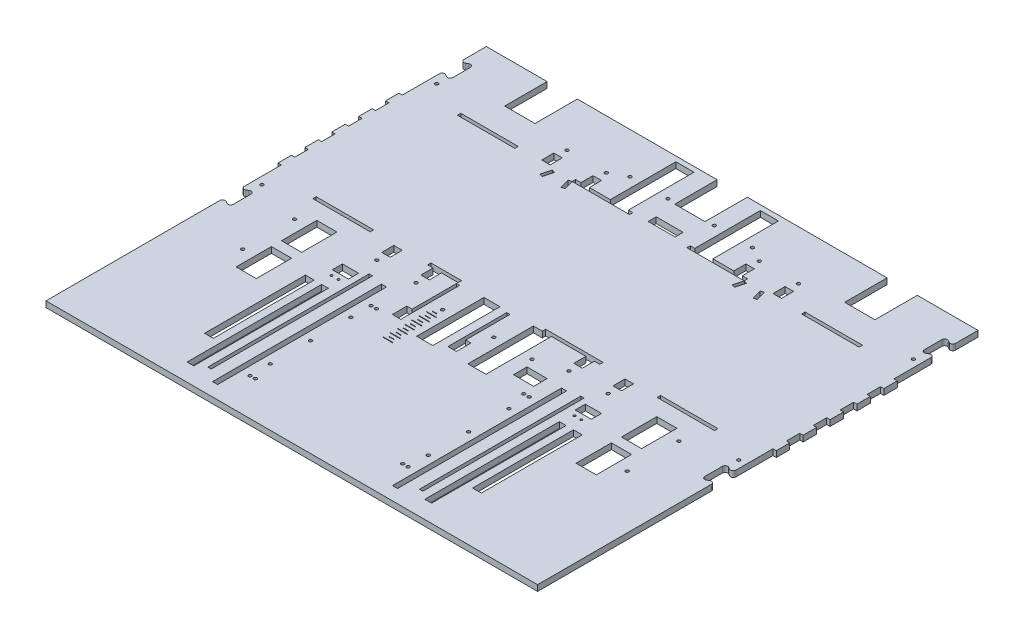
SolidWorks part; units mm, degrees
note: The reader was unsure of these and kept them because the rebuilt part matched: shared geometry of "Sketch11<3>".
material "Acrylic (Medium-high impact)"
ref_plane "Front Plane" through (0, 0, 0) normal (0, 0, 1) x (1, 0, 0)
ref_plane "Top Plane" through (0, 0, 0) normal (0, 1, 0) x (1, 0, 0)
ref_plane "Right Plane" through (0, 0, 0) normal (1, 0, 0) x (0, 0, -1)
sketch "Sketch1" plane through (0, 0, 0) normal (0, 1, 0) x (1, 0, 0)
  line L0 (0, 136.525) -> (0, -165.1) construction
  line L1 (-406.4, 136.525) -> (406.4, 136.525)
  line L2 (-406.4, 136.525) -> (-406.4, -165.1)
  line L3 (-406.4, -165.1) -> (406.4, -165.1)
  line L4 (406.4, 136.525) -> (406.4, -165.1)
  line L5 (-352.2133, 69.85) -> (-352.2133, 66.675)
  line L6 (-406.4, 69.85) -> (-352.2133, 69.85)
  line L7 (-406.4, 69.85) -> (-406.4, 66.675)
  line L8 (-406.4, 66.675) -> (-352.2133, 66.675)
  line L9 (-352.2133, 69.85) -> (-352.2133, 66.675)
  line L10 (-406.4, -66.675) -> (-352.2133, -66.675)
  line L11 (-406.4, -66.675) -> (-406.4, -69.85)
  line L12 (-406.4, -69.85) -> (-352.2133, -69.85)
  line L13 (-352.2133, -66.675) -> (-352.2133, -69.85)
  line L14 (-352.2133, 69.85) -> (-298.0267, 69.85)
  line L15 (-298.0267, 69.85) -> (-298.0267, 66.675)
  line L16 (-352.2133, 66.675) -> (-298.0267, 66.675)
  line L17 (-352.2133, -66.675) -> (-352.2133, -69.85)
  line L18 (-352.2133, -66.675) -> (-298.0267, -66.675)
  line L19 (-298.0267, -66.675) -> (-298.0267, -69.85)
  line L20 (-352.2133, -69.85) -> (-298.0267, -69.85)
  line L21 (-298.0267, 69.85) -> (-298.0267, 66.675)
  line L22 (-298.0267, 69.85) -> (-243.84, 69.85)
  line L23 (-243.84, 69.85) -> (-243.84, 66.675)
  line L24 (-298.0267, 66.675) -> (-243.84, 66.675)
  line L25 (-298.0267, -66.675) -> (-298.0267, -69.85)
  line L26 (-298.0267, -66.675) -> (-243.84, -66.675)
  line L27 (-243.84, -66.675) -> (-243.84, -69.85)
  line L28 (-298.0267, -69.85) -> (-243.84, -69.85)
  line L29 (-243.84, 69.85) -> (-243.84, 66.675)
  line L30 (-243.84, 69.85) -> (-189.6533, 69.85)
  line L31 (-189.6533, 69.85) -> (-189.6533, 66.675)
  line L32 (-243.84, 66.675) -> (-189.6533, 66.675)
  line L33 (-243.84, -66.675) -> (-243.84, -69.85)
  line L34 (-243.84, -66.675) -> (-189.6533, -66.675)
  line L35 (-189.6533, -66.675) -> (-189.6533, -69.85)
  line L36 (-243.84, -69.85) -> (-189.6533, -69.85)
  line L37 (-189.6533, 69.85) -> (-189.6533, 66.675)
  line L38 (-189.6533, 69.85) -> (-135.4667, 69.85)
  line L39 (-135.4667, 69.85) -> (-135.4667, 66.675)
  line L40 (-189.6533, 66.675) -> (-135.4667, 66.675)
  line L41 (-189.6533, -66.675) -> (-189.6533, -69.85)
  line L42 (-189.6533, -66.675) -> (-135.4667, -66.675)
  line L43 (-135.4667, -66.675) -> (-135.4667, -69.85)
  line L44 (-189.6533, -69.85) -> (-135.4667, -69.85)
  line L45 (-135.4667, 69.85) -> (-135.4667, 66.675)
  line L46 (-135.4667, 69.85) -> (-81.28, 69.85)
  line L47 (-81.28, 69.85) -> (-81.28, 66.675)
  line L48 (-135.4667, 66.675) -> (-81.28, 66.675)
  line L49 (-135.4667, -66.675) -> (-135.4667, -69.85)
  line L50 (-135.4667, -66.675) -> (-81.28, -66.675)
  line L51 (-81.28, -66.675) -> (-81.28, -69.85)
  line L52 (-135.4667, -69.85) -> (-81.28, -69.85)
  line L53 (-81.28, 69.85) -> (-81.28, 66.675)
  line L54 (-81.28, 69.85) -> (-27.0933, 69.85)
  line L55 (-27.0933, 69.85) -> (-27.0933, 66.675)
  line L56 (-81.28, 66.675) -> (-27.0933, 66.675)
  line L57 (-81.28, -66.675) -> (-81.28, -69.85)
  line L58 (-81.28, -66.675) -> (-27.0933, -66.675)
  line L59 (-27.0933, -66.675) -> (-27.0933, -69.85)
  line L60 (-81.28, -69.85) -> (-27.0933, -69.85)
  line L61 (-27.0933, 69.85) -> (-27.0933, 66.675)
  line L62 (-27.0933, 69.85) -> (27.0933, 69.85)
  line L63 (27.0933, 69.85) -> (27.0933, 66.675)
  line L64 (-27.0933, 66.675) -> (27.0933, 66.675)
  line L65 (-27.0933, -66.675) -> (-27.0933, -69.85)
  line L66 (-27.0933, -66.675) -> (27.0933, -66.675)
  line L67 (27.0933, -66.675) -> (27.0933, -69.85)
  line L68 (-27.0933, -69.85) -> (27.0933, -69.85)
  line L69 (27.0933, 69.85) -> (27.0933, 66.675)
  line L70 (27.0933, 69.85) -> (81.28, 69.85)
  line L71 (81.28, 69.85) -> (81.28, 66.675)
  line L72 (27.0933, 66.675) -> (81.28, 66.675)
  line L73 (27.0933, -66.675) -> (27.0933, -69.85)
  line L74 (27.0933, -66.675) -> (81.28, -66.675)
  line L75 (81.28, -66.675) -> (81.28, -69.85)
  line L76 (27.0933, -69.85) -> (81.28, -69.85)
  line L77 (81.28, 69.85) -> (81.28, 66.675)
  line L78 (81.28, 69.85) -> (135.4667, 69.85)
  line L79 (135.4667, 69.85) -> (135.4667, 66.675)
  line L80 (81.28, 66.675) -> (135.4667, 66.675)
  line L81 (81.28, -66.675) -> (81.28, -69.85)
  line L82 (81.28, -66.675) -> (135.4667, -66.675)
  line L83 (135.4667, -66.675) -> (135.4667, -69.85)
  line L84 (81.28, -69.85) -> (135.4667, -69.85)
  line L85 (135.4667, 69.85) -> (135.4667, 66.675)
  line L86 (135.4667, 69.85) -> (189.6533, 69.85)
  line L87 (189.6533, 69.85) -> (189.6533, 66.675)
  line L88 (135.4667, 66.675) -> (189.6533, 66.675)
  line L89 (135.4667, -66.675) -> (135.4667, -69.85)
  line L90 (135.4667, -66.675) -> (189.6533, -66.675)
  line L91 (189.6533, -66.675) -> (189.6533, -69.85)
  line L92 (135.4667, -69.85) -> (189.6533, -69.85)
  line L93 (189.6533, 69.85) -> (189.6533, 66.675)
  line L94 (189.6533, 69.85) -> (243.84, 69.85)
  line L95 (243.84, 69.85) -> (243.84, 66.675)
  line L96 (189.6533, 66.675) -> (243.84, 66.675)
  line L97 (189.6533, -66.675) -> (189.6533, -69.85)
  line L98 (189.6533, -66.675) -> (243.84, -66.675)
  line L99 (243.84, -66.675) -> (243.84, -69.85)
  line L100 (189.6533, -69.85) -> (243.84, -69.85)
  line L101 (243.84, 69.85) -> (243.84, 66.675)
  line L102 (243.84, 69.85) -> (298.0267, 69.85)
  line L103 (298.0267, 69.85) -> (298.0267, 66.675)
  line L104 (243.84, 66.675) -> (298.0267, 66.675)
  line L105 (243.84, -66.675) -> (243.84, -69.85)
  line L106 (243.84, -66.675) -> (298.0267, -66.675)
  line L107 (298.0267, -66.675) -> (298.0267, -69.85)
  line L108 (243.84, -69.85) -> (298.0267, -69.85)
  line L109 (298.0267, 69.85) -> (298.0267, 66.675)
  line L110 (298.0267, 69.85) -> (352.2133, 69.85)
  line L111 (352.2133, 69.85) -> (352.2133, 66.675)
  line L112 (298.0267, 66.675) -> (352.2133, 66.675)
  line L113 (298.0267, -66.675) -> (298.0267, -69.85)
  line L114 (298.0267, -66.675) -> (352.2133, -66.675)
  line L115 (352.2133, -66.675) -> (352.2133, -69.85)
  line L116 (298.0267, -69.85) -> (352.2133, -69.85)
  line L117 (352.2133, 69.85) -> (352.2133, 66.675)
  line L118 (352.2133, 69.85) -> (406.4, 69.85)
  line L119 (406.4, 69.85) -> (406.4, 66.675)
  line L120 (352.2133, 66.675) -> (406.4, 66.675)
  line L121 (352.2133, -66.675) -> (352.2133, -69.85)
  line L122 (352.2133, -66.675) -> (406.4, -66.675)
  line L123 (406.4, -66.675) -> (406.4, -69.85)
  line L124 (352.2133, -69.85) -> (406.4, -69.85)
  line L125 (-54.1867, 66.675) -> (-54.1867, -66.675) construction
  line L126 (-381, 57.15) -> (-381, 44.45)
  line L127 (-381, 69.85) -> (-377.825, 69.85)
  line L128 (-381, 69.85) -> (-381, 57.15)
  line L129 (-381, 57.15) -> (-377.825, 57.15)
  line L130 (-377.825, 69.85) -> (-377.825, 57.15)
  line L131 (377.825, 69.85) -> (381, 69.85)
  line L132 (377.825, 69.85) -> (377.825, 57.15)
  line L133 (377.825, 57.15) -> (381, 57.15)
  line L134 (381, 69.85) -> (381, 57.15)
  line L135 (-381, 57.15) -> (-377.825, 57.15)
  line L136 (-377.825, 57.15) -> (-377.825, 44.45)
  line L137 (-381, 44.45) -> (-377.825, 44.45)
  line L138 (377.825, 57.15) -> (377.825, 44.45)
  line L139 (377.825, 57.15) -> (381, 57.15)
  line L140 (381, 57.15) -> (381, 44.45)
  line L141 (377.825, 44.45) -> (381, 44.45)
  line L142 (-381, 44.45) -> (-381, 31.75)
  line L143 (-381, 44.45) -> (-377.825, 44.45)
  line L144 (-377.825, 44.45) -> (-377.825, 31.75)
  line L145 (-381, 31.75) -> (-377.825, 31.75)
  line L146 (377.825, 44.45) -> (377.825, 31.75)
  line L147 (377.825, 44.45) -> (381, 44.45)
  line L148 (381, 44.45) -> (381, 31.75)
  line L149 (377.825, 31.75) -> (381, 31.75)
  line L150 (-381, 31.75) -> (-381, 19.05)
  line L151 (-381, 31.75) -> (-377.825, 31.75)
  line L152 (-377.825, 31.75) -> (-377.825, 19.05)
  line L153 (-381, 19.05) -> (-377.825, 19.05)
  line L154 (377.825, 31.75) -> (377.825, 19.05)
  line L155 (377.825, 31.75) -> (381, 31.75)
  line L156 (381, 31.75) -> (381, 19.05)
  line L157 (377.825, 19.05) -> (381, 19.05)
  line L158 (-381, 19.05) -> (-381, 6.35)
  line L159 (-381, 19.05) -> (-377.825, 19.05)
  line L160 (-377.825, 19.05) -> (-377.825, 6.35)
  line L161 (-381, 6.35) -> (-377.825, 6.35)
  line L162 (377.825, 19.05) -> (377.825, 6.35)
  line L163 (377.825, 19.05) -> (381, 19.05)
  line L164 (381, 19.05) -> (381, 6.35)
  line L165 (377.825, 6.35) -> (381, 6.35)
  line L166 (-381, 6.35) -> (-381, -6.35)
  line L167 (-381, 6.35) -> (-377.825, 6.35)
  line L168 (-377.825, 6.35) -> (-377.825, -6.35)
  line L169 (-381, -6.35) -> (-377.825, -6.35)
  line L170 (377.825, 6.35) -> (377.825, -6.35)
  line L171 (377.825, 6.35) -> (381, 6.35)
  line L172 (381, 6.35) -> (381, -6.35)
  line L173 (377.825, -6.35) -> (381, -6.35)
  line L174 (-381, -6.35) -> (-381, -19.05)
  line L175 (-381, -6.35) -> (-377.825, -6.35)
  line L176 (-377.825, -6.35) -> (-377.825, -19.05)
  line L177 (-381, -19.05) -> (-377.825, -19.05)
  line L178 (377.825, -6.35) -> (377.825, -19.05)
  line L179 (377.825, -6.35) -> (381, -6.35)
  line L180 (381, -6.35) -> (381, -19.05)
  line L181 (377.825, -19.05) -> (381, -19.05)
  line L182 (-381, -19.05) -> (-381, -31.75)
  line L183 (-381, -19.05) -> (-377.825, -19.05)
  line L184 (-377.825, -19.05) -> (-377.825, -31.75)
  line L185 (-381, -31.75) -> (-377.825, -31.75)
  line L186 (377.825, -19.05) -> (377.825, -31.75)
  line L187 (377.825, -19.05) -> (381, -19.05)
  line L188 (381, -19.05) -> (381, -31.75)
  line L189 (377.825, -31.75) -> (381, -31.75)
  line L190 (-381, -31.75) -> (-381, -44.45)
  line L191 (-381, -31.75) -> (-377.825, -31.75)
  line L192 (-377.825, -31.75) -> (-377.825, -44.45)
  line L193 (-381, -44.45) -> (-377.825, -44.45)
  line L194 (377.825, -31.75) -> (377.825, -44.45)
  line L195 (377.825, -31.75) -> (381, -31.75)
  line L196 (381, -31.75) -> (381, -44.45)
  line L197 (377.825, -44.45) -> (381, -44.45)
  line L198 (-381, -44.45) -> (-381, -57.15)
  line L199 (-381, -44.45) -> (-377.825, -44.45)
  line L200 (-377.825, -44.45) -> (-377.825, -57.15)
  line L201 (-381, -57.15) -> (-377.825, -57.15)
  line L202 (377.825, -44.45) -> (377.825, -57.15)
  line L203 (377.825, -44.45) -> (381, -44.45)
  line L204 (381, -44.45) -> (381, -57.15)
  line L205 (377.825, -57.15) -> (381, -57.15)
  line L206 (-381, -57.15) -> (-381, -69.85)
  line L207 (-381, -57.15) -> (-377.825, -57.15)
  line L208 (-377.825, -57.15) -> (-377.825, -69.85)
  line L209 (-381, -69.85) -> (-377.825, -69.85)
  line L210 (377.825, -57.15) -> (377.825, -69.85)
  line L211 (377.825, -57.15) -> (381, -57.15)
  line L212 (381, -57.15) -> (381, -69.85)
  line L213 (377.825, -69.85) -> (381, -69.85)
  line L214 (-377.825, 0) -> (377.825, 0) construction
  point P23 (-54.1867, 0)
  point P133 (0, 0)
  dimension "D1" = 301.625
  dimension "D2" = 812.8
  dimension "D3" = 3.175
  dimension "D5" = 54.1867
  dimension "D6" = 66.675
  dimension "D7" = 133.35
  dimension "D9" = 12.7
  dimension "D10" = 755.65
  dimension "D4" = 15
  dimension "D8" = 11
extrude "Main Extrude" add sketch "Sketch1" along normal blind 5.588 contours L124 L116 L108 L100 L92 L84 L76 L68 L60 L52 L44 L36 L28 L20 L12 L2 L3 L4 | L210 L202 L194 L186 L178 L170 L162 L154 L146 L138 L132 L120 L112 L104 L96 L88 L80 L72 L64 L56 L48 L40 L32 L24 L16 L8 L130 L136 L144 L152 L160 L168 L176 L184 L192 L200 L208 L10 L18 L26 L34 L42 L50 L58 L66 L74 L82 L90 L98 L106 L114 | L110 L118 L4 L1 L2 L6 L14 L22 L30 L38 L46 L54 L62 L70 L78 L86 L94 L102 | L206 L198 L190 L182 L174 L166 L158 L150 L142 L126 L128 L8 L2 L10 | L204 L212 L122 L4 L120 L134 L140 L148 L156 L164 L172 L180 L188 L196 | L126 L137 L136 L129 | L150 L153 L152 L145 | L166 L169 L168 L161 | L182 L185 L184 L177 | L198 L201 L200 L193 | L13 L20 L19 L18 | L5 L16 L15 L14 | L23 L32 L31 L30 | L27 L36 L35 L34 | L43 L52 L51 L50 | L39 L48 L47 L46 | L55 L64 L63 L62 | L59 L68 L67 L66 | L71 L80 L79 L78 | L75 L84 L83 L82 | L87 L96 L95 L94 | L103 L112 L111 L110 | L91 L100 L99 L98 | L107 L116 L115 L114 | L138 L141 L140 L133 | L154 L157 L156 L149 | L170 L173 L172 L165 | L186 L189 L188 L181 | L202 L205 L204 L197
sketch "Sketch2" plane through (0, 5.588, 0) normal (0, 1, 0) x (1, 0, 0)
  line L0 (-90.678, 66.675) -> (-90.678, -110.1521) construction
  line L1 (-81.28, 66.675) -> (-27.0933, 66.675) construction
  line L3 (90.678, 66.675) -> (90.678, -110.1521) construction
  line L4 (27.0933, 66.675) -> (81.28, 66.675) construction
  line L5 (-90.678, -21.7386) -> (90.678, -21.7386) construction
  line L6 (-81.28, -66.675) -> (-27.0933, -66.675) construction
  line L7 (-52.578, -66.675) -> (-1.778, -66.675) construction
  line L8 (-52.578, -66.675) -> (-52.578, -36.2354) construction
  line L9 (-52.578, -36.2354) -> (-1.778, -36.2354) construction
  line L10 (-1.778, -66.675) -> (-1.778, -36.2354) construction
  line L11 (-26.543, 63.5) -> (26.543, 63.5) construction
  line L12 (13.843, -60.325) -> (40.513, -60.325) construction
  line L13 (13.843, -60.325) -> (13.843, -66.675) construction
  line L14 (13.843, -66.675) -> (40.513, -66.675) construction
  line L15 (40.513, -60.325) -> (40.513, -66.675) construction
  line L16 (-53.213, 66.675) -> (-26.543, 66.675) construction
  line L17 (-53.213, 66.675) -> (-53.213, 60.325) construction
  line L18 (-53.213, 60.325) -> (-26.543, 60.325) construction
  line L19 (-26.543, 66.675) -> (-26.543, 60.325) construction
  line L20 (26.543, 66.675) -> (53.213, 66.675) construction
  line L21 (26.543, 66.675) -> (26.543, 60.325) construction
  line L22 (26.543, 60.325) -> (53.213, 60.325) construction
  line L23 (53.213, 66.675) -> (53.213, 60.325) construction
  line L24 (27.0933, -66.675) -> (81.28, -66.675) construction
  point P4 (0, -21.7386)
  point P23 (-27.178, -36.2354)
  point P24 (27.178, -60.325)
  point P34 (0, 63.5)
  point P35 (-39.878, 66.675)
  dimension "D1" = 181.356
  dimension "D2" = 50.8
  dimension "D3" = 63.5
  dimension "D4" = 26.67
  dimension "D5" = 63.5
  dimension "D6" = 50.8
  dimension "D7" = 6.35
sketch "Sketch3" plane through (0, 5.588, 0) normal (0, 1, 0) x (1, 0, 0)
  line L1 (-52.578, -66.675) -> (-27.0933, -66.675)
  line L2 (-52.578, -66.675) -> (-52.578, -69.85)
  line L3 (-52.578, -69.85) -> (-27.0933, -69.85)
  line L4 (-27.0933, -66.675) -> (-27.0933, -69.85)
extrude "Under Trough Fill" add sketch "Sketch3" against normal up to surface (5.588 mm away) up to face at (0, 0, 1.5875)
sketch "Sketch4" plane through (0, 5.588, 0) normal (0, 1, 0) x (1, 0, 0)
  line L0 (-39.878, 66.675) -> (39.878, 66.675) construction
  line L2 (-406.4, 136.525) -> (406.4, 136.525) construction
  line L3 (27.0933, -69.85) -> (81.28, -69.85) construction
  line L4 (27.0933, 66.675) -> (81.28, 66.675) construction
  line L5 (27.178, -131.7625) -> (27.178, -66.675) construction
  line L6 (13.843, -66.675) -> (40.513, -66.675) construction
  line L7 (39.878, 131.7625) -> (39.878, 66.675) construction
  line L8 (-406.4, 66.675) -> (-406.4, -66.675) construction
  line L9 (-39.878, 131.7625) -> (-39.878, 66.675) construction
  line L11 (-406.4, -66.675) -> (-381, -66.675) construction
  line L12 (-400.05, -66.675) -> (-387.35, -66.675)
  line L13 (-400.05, -66.675) -> (-400.05, -63.5)
  line L14 (-400.05, -63.5) -> (-387.35, -63.5)
  line L15 (-387.35, -66.675) -> (-387.35, -63.5)
  line L16 (-406.4, 66.675) -> (-381, 66.675) construction
  line L17 (-400.05, 66.675) -> (-387.35, 66.675)
  line L18 (-400.05, 66.675) -> (-400.05, 63.5)
  line L19 (-400.05, 63.5) -> (-387.35, 63.5)
  line L20 (-387.35, 66.675) -> (-387.35, 63.5)
  line L21 (381, 66.675) -> (406.4, 66.675) construction
  line L22 (387.35, 66.675) -> (400.05, 66.675)
  line L23 (387.35, 66.675) -> (387.35, 63.5)
  line L24 (387.35, 63.5) -> (400.05, 63.5)
  line L25 (400.05, 66.675) -> (400.05, 63.5)
  line L26 (381, -66.675) -> (406.4, -66.675) construction
  line L27 (387.35, -66.675) -> (400.05, -66.675)
  line L28 (387.35, -66.675) -> (387.35, -63.5)
  line L29 (387.35, -63.5) -> (400.05, -63.5)
  line L30 (400.05, -66.675) -> (400.05, -63.5)
  line L35 (406.4, 66.675) -> (406.4, -66.675) construction
  line L36 (-81.28, 69.85) -> (-27.0933, 69.85) construction
  line L39 (27.0933, 69.85) -> (81.28, 69.85) construction
  line L40 (18.628, -69.85) -> (35.728, -69.85)
  line L41 (18.628, -69.85) -> (18.628, -131.7625)
  line L42 (18.628, -131.7625) -> (35.728, -131.7625)
  line L43 (35.728, -69.85) -> (35.728, -131.7625)
  line L44 (31.328, 131.7625) -> (48.428, 131.7625)
  line L45 (31.328, 131.7625) -> (31.328, 69.85)
  line L46 (31.328, 69.85) -> (48.428, 69.85)
  line L47 (48.428, 131.7625) -> (48.428, 69.85)
  line L48 (9.178, -97.7625) -> (45.178, -97.7625) construction
  line L49 (-48.428, 131.7625) -> (-31.328, 131.7625)
  line L50 (-48.428, 131.7625) -> (-48.428, 69.85)
  line L51 (-48.428, 69.85) -> (-31.328, 69.85)
  line L52 (-31.328, 131.7625) -> (-31.328, 69.85)
  line L53 (-57.878, 97.7625) -> (-21.878, 97.7625) construction
  line L54 (21.878, 97.7625) -> (57.878, 97.7625) construction
  circle A12 centre (9.178, -97.7625) radius 1.5
  circle A13 centre (45.178, -97.7625) radius 1.5
  circle A14 centre (21.878, 97.7625) radius 1.5
  circle A15 centre (57.878, 97.7625) radius 1.5
  circle A16 centre (-21.878, 97.7625) radius 1.5
  circle A17 centre (-57.878, 97.7625) radius 1.5
  point P2 (0, 136.525)
  point P3 (0, 66.675)
  point P59 (-393.7, -63.5)
  point P62 (393.7, -66.675)
  point P73 (27.178, -69.85)
  point P87 (39.878, 131.7625)
  point P92 (-39.878, 131.7625)
  point P100 (27.178, -97.7625)
  point P106 (-39.878, 97.7625)
  point P107 (39.878, 97.7625)
  dimension "D2" = 62.656
  dimension "D15" = 3
  dimension "D4" = 12.7
  dimension "D5" = 3.175
  dimension "D6" = 12.7
  dimension "D7" = 12.7
  dimension "D12" = 17.1
  dimension "D13" = 61.9125
  dimension "D14" = 36
  dimension "D16" = 27.9125
  dimension "D17" = 27.9125
extrude "Lever Holes" cut sketch "Sketch4" against normal through all
sketch "Sketch5" plane through (0, 5.588, 0) normal (0, 1, 0) x (1, 0, 0)
  line L0 (-20.498, -133.35) -> (-20.498, -69.85) construction
  line L1 (-49.428, -99.2124) -> (-4.928, -99.2124) construction
  line L2 (-52.428, -127) -> (-49.428, -127)
  line L3 (-52.428, -127) -> (-52.428, -71.4248)
  line L4 (-52.428, -71.4248) -> (-49.428, -71.4248)
  line L5 (-49.428, -127) -> (-49.428, -71.4248)
  line L6 (-4.928, -127) -> (-1.928, -127)
  line L7 (-4.928, -127) -> (-4.928, -71.4248)
  line L8 (-4.928, -71.4248) -> (-1.928, -71.4248)
  line L9 (-1.928, -127) -> (-1.928, -71.4248)
  line L10 (-27.178, -66.675) -> (-27.178, -99.2124) construction
  line L11 (-52.578, -66.675) -> (-1.778, -66.675) construction
  line L12 (-28.118, -69.85) -> (-12.878, -69.85)
  line L13 (-81.28, -69.85) -> (-52.578, -69.85) construction
  line L14 (-55.778, -71.9185) -> (-4.928, -71.9185) construction
  line L15 (-28.118, -69.85) -> (-28.118, -133.35)
  line L16 (-52.578, -66.675) -> (-52.578, -69.85) construction
  line L17 (-52.428, -127) -> (-57.428, -127)
  line L18 (-52.428, -127) -> (-52.428, -113.3)
  line L19 (-52.428, -113.3) -> (-57.428, -113.3)
  line L20 (-57.428, -127) -> (-57.428, -113.3)
  line L21 (-1.928, -127) -> (3.072, -127)
  line L22 (-1.928, -127) -> (-1.928, -113.3)
  line L23 (-1.928, -113.3) -> (3.072, -113.3)
  line L24 (3.072, -127) -> (3.072, -113.3)
  line L25 (-52.578, -66.675) -> (-52.428, -66.675)
  line L26 (-52.578, -66.675) -> (-52.578, -69.85)
  line L27 (-52.578, -69.85) -> (-52.428, -69.85)
  line L28 (-52.428, -66.675) -> (-52.428, -69.85)
  line L29 (-28.118, -133.35) -> (-12.878, -133.35)
  line L30 (-12.878, -69.85) -> (-12.878, -133.35)
  line L31 (-81.28, -69.85) -> (-52.578, -69.85) construction
  circle A0 centre (-3.428, -99.35) radius 1.5
  circle A2 centre (-37.568, -99.35) radius 1.5
  point P19 (-50.928, -127)
  point P20 (-3.428, -127)
  dimension "D6" = 3
  dimension "D1" = 3
  dimension "D3" = 47.5
  dimension "D4" = 57.15
  dimension "D7" = 5
  dimension "D8" = 13.7
  dimension "D2" = 1.5748
  dimension "D5" = 15.24
  dimension "D9" = 63.5
  dimension "D10" = 7.95
  dimension "D11" = 9.45
  dimension "D12" = 34
extrude "Trough Slot" cut sketch "Sketch5" against normal through all
sketch "Sketch6" plane through (0, 5.588, 0) normal (0, 1, 0) x (1, 0, 0)
  line L0 (90.678, -130.35) -> (103.378, -130.35) construction
  line L1 (-114.6905, -123.85) -> (114.6905, -123.85) construction
  line L3 (-81.28, -69.85) -> (-52.428, -69.85) construction
  line L4 (111.4405, -123.85) -> (117.9405, -123.85) construction
  line L5 (95.4405, -130.35) -> (95.4405, -83.0238) construction
  line L6 (90.678, 66.675) -> (90.678, -110.1521) construction
  line L7 (0, -21.7386) -> (0, -165.1) construction
  line L8 (-90.678, -21.7386) -> (90.678, -21.7386) construction
  line L9 (-406.4, -165.1) -> (406.4, -165.1) construction
  line L20 (-117.9405, -123.85) -> (-111.4405, -123.85) construction
  line L21 (-122.3105, -109.245) -> (-107.0705, -109.245)
  line L22 (-122.3105, -109.245) -> (-122.3105, -118.77)
  line L23 (-122.3105, -118.77) -> (-107.0705, -118.77)
  line L24 (-107.0705, -109.245) -> (-107.0705, -118.77)
  line L25 (107.0705, -109.245) -> (122.3105, -109.245)
  line L26 (107.0705, -109.245) -> (107.0705, -118.77)
  line L27 (107.0705, -118.77) -> (122.3105, -118.77)
  line L28 (122.3105, -109.245) -> (122.3105, -118.77)
  line L29 (-114.6905, -118.77) -> (-114.6905, -123.85) construction
  line L30 (114.6905, -118.77) -> (114.6905, -123.85) construction
  circle A0 centre (117.9405, -123.85) radius 1.05
  circle A1 centre (111.4405, -123.85) radius 1.05
  circle A10 centre (-117.9405, -123.85) radius 1.05
  circle A11 centre (-111.4405, -123.85) radius 1.05
  point P0 (108.1405, -130.35)
  point P11 (0, -123.85)
  dimension "D5" = 2.1
  dimension "D2" = 60.5
  dimension "D3" = 6.5
  dimension "D4" = 12.7
  dimension "D6" = 6.5
  dimension "D7" = 4.7625
  dimension "D8" = 3.3
  dimension "D9" = 5.08
  dimension "D10" = 9.525
  dimension "D11" = 15.24
extrude "Close Switch Holes" cut sketch "Sketch6" against normal through all
sketch "Sketch7" plane through (0, 5.588, 0) normal (0, 1, 0) x (1, 0, 0)
  line L0 (-38.773, -149.85) -> (-38.773, -105.4) construction
  line L1 (-49.428, -127) -> (-28.118, -127) construction
  line L2 (-49.428, -127) -> (-49.428, -71.4248) construction
  line L4 (-28.118, -69.85) -> (-28.118, -133.35) construction
  line L9 (-81.28, -69.85) -> (-52.428, -69.85) construction
  line L10 (-43.5355, -142.738) -> (-43.5355, -143.246)
  line L15 (-43.5355, -149.596) -> (-34.0105, -149.596)
  line L16 (-43.5355, -149.596) -> (-43.5355, -150.104)
  line L21 (-43.5355, -150.104) -> (-34.0105, -150.104)
  line L22 (-34.0105, -149.596) -> (-34.0105, -150.104)
  line L27 (-43.5355, -149.596) -> (-34.0105, -150.104) construction
  line L28 (-43.5355, -150.104) -> (-34.0105, -149.596) construction
  line L33 (-41.1542, -146.421) -> (-36.3917, -146.421)
  line L34 (-41.1542, -146.421) -> (-41.1542, -146.929)
  line L39 (-41.1542, -146.929) -> (-36.3917, -146.929)
  line L40 (-36.3917, -146.421) -> (-36.3917, -146.929)
  line L45 (-41.1542, -146.421) -> (-36.3917, -146.929) construction
  line L46 (-41.1542, -146.929) -> (-36.3917, -146.421) construction
  line L51 (-43.5355, -142.738) -> (-34.0105, -142.738)
  line L52 (-34.0105, -142.738) -> (-34.0105, -143.246)
  line L57 (-43.5355, -143.246) -> (-34.0105, -143.246)
  line L58 (-41.1542, -139.563) -> (-41.1542, -140.071)
  line L63 (-41.1542, -139.563) -> (-36.3917, -139.563)
  line L64 (-36.3917, -139.563) -> (-36.3917, -140.071)
  line L69 (-41.1542, -140.071) -> (-36.3917, -140.071)
  line L70 (-43.5355, -135.88) -> (-43.5355, -136.388)
  line L75 (-43.5355, -135.88) -> (-34.0105, -135.88)
  line L76 (-34.0105, -135.88) -> (-34.0105, -136.388)
  line L81 (-43.5355, -136.388) -> (-34.0105, -136.388)
  line L82 (-41.1543, -132.705) -> (-41.1543, -133.213)
  line L83 (-41.1543, -132.705) -> (-36.3918, -132.705)
  line L84 (-36.3918, -132.705) -> (-36.3918, -133.213)
  line L85 (-41.1543, -133.213) -> (-36.3918, -133.213)
  line L86 (-43.5355, -129.022) -> (-43.5355, -129.53)
  line L87 (-43.5355, -129.022) -> (-34.0105, -129.022)
  line L88 (-34.0105, -129.022) -> (-34.0105, -129.53)
  line L89 (-43.5355, -129.53) -> (-34.0105, -129.53)
  line L90 (-41.1543, -125.847) -> (-41.1543, -126.355)
  line L91 (-41.1543, -125.847) -> (-36.3918, -125.847)
  line L92 (-36.3918, -125.847) -> (-36.3918, -126.355)
  line L93 (-41.1543, -126.355) -> (-36.3918, -126.355)
  line L94 (-43.5355, -122.164) -> (-43.5355, -122.672)
  line L95 (-43.5355, -122.164) -> (-34.0105, -122.164)
  line L96 (-34.0105, -122.164) -> (-34.0105, -122.672)
  line L97 (-43.5355, -122.672) -> (-34.0105, -122.672)
  line L98 (-41.1543, -118.989) -> (-41.1543, -119.497)
  line L99 (-41.1543, -118.989) -> (-36.3918, -118.989)
  line L100 (-36.3918, -118.989) -> (-36.3918, -119.497)
  line L101 (-41.1543, -119.497) -> (-36.3918, -119.497)
  line L102 (-43.5355, -115.306) -> (-43.5355, -115.814)
  line L103 (-43.5355, -115.306) -> (-34.0105, -115.306)
  line L104 (-34.0105, -115.306) -> (-34.0105, -115.814)
  line L105 (-43.5355, -115.814) -> (-34.0105, -115.814)
  line L106 (-41.1543, -112.131) -> (-41.1543, -112.639)
  line L107 (-41.1543, -112.131) -> (-36.3918, -112.131)
  line L108 (-36.3918, -112.131) -> (-36.3918, -112.639)
  line L109 (-41.1543, -112.639) -> (-36.3918, -112.639)
  line L130 (-28.5048, -105.4) -> (-38.773, -105.4) construction
  line L136 (-43.5355, -108.448) -> (-43.5355, -108.956)
  line L137 (-43.5355, -108.448) -> (-34.0105, -108.448)
  line L138 (-34.0105, -108.448) -> (-34.0105, -108.956)
  line L139 (-43.5355, -108.956) -> (-34.0105, -108.956)
  line L140 (-41.1543, -105.273) -> (-41.1543, -105.781)
  line L141 (-41.1543, -105.273) -> (-36.3918, -105.273)
  line L142 (-36.3918, -105.273) -> (-36.3918, -105.781)
  line L143 (-41.1543, -105.781) -> (-36.3918, -105.781)
  point P2 (-38.773, -146.675)
  point P16 (-41.1542, -146.675)
  point P17 (-43.5355, -149.85)
  point P65 (-38.773, -127)
  dimension "D1" = 80
  dimension "D2" = 44.45
  dimension "D3" = 0.508
  dimension "D4" = 9.525
  dimension "D5" = 3.175
  dimension "D6" = 4.7625
  dimension "D8" = 3.175
  dimension "D7" = 7
extrude "Trough Measurement" cut sketch "Sketch7" against normal through all
sketch "Sketch8" plane through (0, 5.588, 0) normal (0, 1, 0) x (1, 0, 0)
  line L0 (160.528, 96.525) -> (160.528, -85.725) construction
  line L1 (49.063, -106.3625) -> (68.113, -106.3625)
  line L2 (49.063, -106.3625) -> (49.063, -119.0625)
  line L3 (49.063, -119.0625) -> (68.113, -119.0625)
  line L4 (68.113, -106.3625) -> (68.113, -119.0625)
  line L5 (35.728, -131.7625) -> (35.728, -69.85) construction
  line L6 (135.4667, -69.85) -> (189.6533, -69.85) construction
  line L15 (-406.4, 136.525) -> (406.4, 136.525) construction
  line L16 (-31.328, 123) -> (31.328, 123) construction
  line L17 (-31.328, 69.85) -> (-31.328, 131.7625) construction
  line L18 (31.328, 131.7625) -> (31.328, 69.85) construction
  line L19 (0, 77.47) -> (0, 96.525) construction
  line L20 (18.628, -131.7625) -> (35.728, -131.7625) construction
  line L29 (151.003, -119.0625) -> (170.053, -119.0625)
  line L30 (-174.8155, 136.525) -> (-146.2405, 136.525)
  line L31 (-14.2875, 136.525) -> (14.2875, 136.525)
  line L32 (-14.2875, 136.525) -> (-14.2875, 96.525)
  line L33 (-14.2875, 96.525) -> (14.2875, 96.525)
  line L34 (14.2875, 136.525) -> (14.2875, 96.525)
  line L35 (-12.7, 69.85) -> (12.7, 69.85)
  line L36 (-12.7, 69.85) -> (-12.7, 77.47)
  line L37 (-12.7, 77.47) -> (12.7, 77.47)
  line L38 (12.7, 69.85) -> (12.7, 77.47)
  line L39 (-31.328, 69.85) -> (-27.0933, 69.85) construction
  line L40 (151.003, -85.725) -> (170.053, -85.725)
  line L41 (151.003, -85.725) -> (151.003, -161.925)
  line L42 (151.003, -161.925) -> (170.053, -161.925)
  line L43 (170.053, -85.725) -> (170.053, -161.925)
  line L44 (-170.053, -85.725) -> (-151.003, -85.725)
  line L45 (-170.053, -85.725) -> (-170.053, -161.925)
  line L46 (-170.053, -161.925) -> (-151.003, -161.925)
  line L47 (-151.003, -85.725) -> (-151.003, -161.925)
  line L48 (90.678, 66.675) -> (90.678, -110.1521) construction
  line L49 (-151.003, -123.825) -> (151.003, -123.825) construction
  line L50 (151.003, -119.0625) -> (151.003, -128.5875)
  line L51 (151.003, -128.5875) -> (170.053, -128.5875)
  line L52 (170.053, -119.0625) -> (170.053, -128.5875)
  line L53 (-170.053, -119.0625) -> (-151.003, -119.0625)
  line L54 (-170.053, -119.0625) -> (-170.053, -128.5875)
  line L55 (-170.053, -128.5875) -> (-151.003, -128.5875)
  line L56 (-151.003, -119.0625) -> (-151.003, -128.5875)
  line L57 (-174.8155, 136.525) -> (-174.8155, 96.525)
  line L58 (-174.8155, 96.525) -> (-146.2405, 96.525)
  line L59 (-146.2405, 136.525) -> (-146.2405, 96.525)
  line L60 (146.2405, 136.525) -> (174.8155, 136.525)
  line L61 (146.2405, 136.525) -> (146.2405, 96.525)
  line L62 (146.2405, 96.525) -> (174.8155, 96.525)
  line L63 (174.8155, 136.525) -> (174.8155, 96.525)
  line L64 (-160.528, 96.525) -> (-160.528, -85.725) construction
  point P6 (58.588, -106.3625)
  point P23 (0, 123)
  point P30 (170.053, -123.825)
  point P31 (170.053, -123.825)
  point P38 (0, 96.525)
  point P61 (0, -123.825)
  dimension "D1" = 19.05
  dimension "D2" = 12.7
  dimension "D3" = 22.86
  dimension "D4" = 12.7
  dimension "D5" = 9.525
  dimension "D6" = 76.2
  dimension "D8" = 40
  dimension "D9" = 28.575
  dimension "D10" = 7.62
  dimension "D11" = 25.4
  dimension "D12" = 15.875
  dimension "D13" = 60.325
  dimension "D15" = 19.05
extrude "Wire Holes" cut sketch "Sketch8" against normal through all contours L55 L45 L46 L47 | L45 L53 L47 L44 | L51 L41 L42 L43 | L43 L40 L41 L29 | L4 L1 L2 L3 | L34 L31 L32 L33 | L35 L38 L37 L36 | L59 L30 L57 L58 | L63 L60 L61 L62
sketch "Sketch9" plane through (0, 5.588, 0) normal (0, 1, 0) x (1, 0, 0)
  line L0 (-109.2096, 89.85) -> (109.2096, 89.85) construction
  line L1 (109.2096, 89.85) -> (109.2096, -89.85) construction
  line L2 (109.2096, -89.85) -> (-109.2096, -89.85) construction
  line L3 (-109.2096, -89.85) -> (-109.2096, 89.85) construction
  line L4 (-162.56, 66.675) -> (-162.56, -66.675) construction
  line L5 (-189.6533, 66.675) -> (-135.4667, 66.675) construction
  line L6 (-189.6533, -66.675) -> (-135.4667, -66.675) construction
  line L7 (-109.2096, 0) -> (-162.56, 0) construction
  line L8 (-90.678, 66.675) -> (-90.678, -110.1521) construction
  line L9 (-189.6533, -69.85) -> (-135.4667, -69.85) construction
  line L10 (-189.6533, 69.85) -> (-135.4667, 69.85) construction
  line L11 (-113.2096, 69.85) -> (-105.2096, 69.85)
  line L12 (-113.2096, 69.85) -> (-113.2096, 81.28)
  line L13 (-113.2096, 81.28) -> (-105.2096, 81.28)
  line L14 (-105.2096, 69.85) -> (-105.2096, 81.28)
  line L16 (105.2096, 81.28) -> (113.2096, 81.28)
  line L17 (105.2096, 81.28) -> (105.2096, 69.85)
  line L18 (105.2096, 69.85) -> (113.2096, 69.85)
  line L19 (113.2096, 81.28) -> (113.2096, 69.85)
  line L20 (105.2096, -69.85) -> (113.2096, -69.85)
  line L21 (105.2096, -69.85) -> (105.2096, -81.28)
  line L22 (105.2096, -81.28) -> (113.2096, -81.28)
  line L23 (113.2096, -69.85) -> (113.2096, -81.28)
  line L24 (-113.2096, -81.28) -> (-105.2096, -81.28)
  line L25 (-113.2096, -81.28) -> (-113.2096, -69.85)
  line L26 (-113.2096, -69.85) -> (-105.2096, -69.85)
  line L27 (-105.2096, -81.28) -> (-105.2096, -69.85)
  circle A0 centre (109.2096, -89.85) radius 1.5
  circle A1 centre (-109.2096, -89.85) radius 1.5
  circle A2 centre (109.2096, 89.85) radius 1.5
  circle A3 centre (-109.2096, 89.85) radius 1.5
  point P8 (0, -89.85)
  point P29 (-109.2096, 81.28)
  point P43 (109.2096, 81.28)
  point P47 (109.2096, -69.85)
  dimension "D1" = 3
  dimension "D2" = 18.5316
  dimension "D3" = 20
  dimension "D4" = 11.43
  dimension "D5" = 8
extrude "IR Slots" cut sketch "Sketch9" against normal through all
sketch "Sketch10" plane through (0, 5.588, 0) normal (0, 1, 0) x (1, 0, 0)
  line L0 (0, 0) -> (0, 69.85) construction
  line L1 (-100.061, 66.675) -> (-96.9942, 65.8532)
  line L2 (-100.061, 66.675) -> (-102.5263, 57.4746)
  line L3 (-102.5263, 57.4746) -> (-99.4594, 56.6528)
  line L4 (-96.9942, 65.8532) -> (-99.4594, 56.6528)
  line L5 (-84.3618, 65.8532) -> (-81.295, 66.675)
  line L6 (-84.3618, 65.8532) -> (-81.8966, 56.6528)
  line L7 (-81.8966, 56.6528) -> (-78.8297, 57.4746)
  line L8 (-81.295, 66.675) -> (-78.8297, 57.4746)
  line L9 (-12.7, 69.85) -> (12.7, 69.85) construction
  line L14 (81.28, 66.675) -> (100.061, 66.675) construction
  line L19 (-90.678, 66.675) -> (-90.678, -110.1521) construction
  line L20 (-98.2268, 61.253) -> (-83.1292, 61.253) construction
  line L21 (-81.28, 66.675) -> (-100.061, 66.675) construction
  line L22 (98.2268, 61.253) -> (83.1292, 61.253) construction
  line L23 (81.295, 66.675) -> (78.8297, 57.4746)
  line L24 (81.8966, 56.6528) -> (78.8297, 57.4746)
  line L25 (84.3618, 65.8532) -> (81.8966, 56.6528)
  line L26 (84.3618, 65.8532) -> (81.295, 66.675)
  line L27 (96.9942, 65.8532) -> (99.4594, 56.6528)
  line L28 (102.5263, 57.4746) -> (99.4594, 56.6528)
  line L29 (100.061, 66.675) -> (102.5263, 57.4746)
  line L30 (100.061, 66.675) -> (96.9942, 65.8532)
  line L31 (-96.9942, 65.8532) -> (-96.774, 66.675) construction
  line L32 (-84.3618, 65.8532) -> (-84.582, 66.675) construction
  line L33 (-90.678, 66.675) -> (-90.678, 61.253) construction
  line L34 (-96.774, 66.675) -> (-95.9233, 69.85) construction
  line L35 (-84.582, 66.675) -> (-85.4327, 69.85) construction
  line L36 (-81.28, 69.85) -> (-95.9233, 69.85) construction
  point P27 (-90.678, 61.253)
  dimension "D1" = 3.175
  dimension "D3" = 9.525
  dimension "D4" = 105
  dimension "D2" = 6.096
extrude "Door Flange Slots" cut sketch "Sketch10" against normal through all
sketch "Sketch12" plane through (0, 5.588, 0) normal (0, 1, 0) x (1, 0, 0)
  line L0 (-253.5873, 82.55) -> (-225.1393, 82.55) construction
  line L1 (-253.5873, -82.55) -> (-225.1393, -82.55) construction
  line L2 (-233.807, 82.55) -> (-233.807, -82.55) construction
  line L3 (-233.807, 0) -> (0, 0) construction
  line L4 (-298.0267, -69.85) -> (-243.84, -69.85) construction
  line L5 (-240.9508, -76.2) -> (-237.7758, -76.2)
  line L6 (-240.9508, -76.2) -> (-240.9507, -88.9)
  line L7 (-240.9507, -88.9) -> (-237.7758, -88.9)
  line L8 (-237.7758, -76.2) -> (-237.7758, -88.9)
  line L9 (-240.9508, 88.9) -> (-237.7758, 88.9)
  line L10 (-240.9508, 88.9) -> (-240.9508, 76.2)
  line L11 (-240.9508, 76.2) -> (-237.7758, 76.2)
  line L12 (-237.7758, 88.9) -> (-237.7758, 76.2)
  line L13 (0, -3.0734) -> (0, 3.0734) construction
  line L14 (233.807, 82.55) -> (233.807, -82.55) construction
  line L15 (253.5873, -82.55) -> (225.1393, -82.55) construction
  line L16 (253.5873, 82.55) -> (225.1393, 82.55) construction
  line L17 (237.7758, 88.9) -> (237.7758, 76.2)
  line L18 (240.9508, 76.2) -> (237.7758, 76.2)
  line L19 (240.9508, 88.9) -> (240.9508, 76.2)
  line L20 (240.9508, 88.9) -> (237.7758, 88.9)
  line L21 (237.7757, -76.2) -> (237.7757, -88.9)
  line L22 (240.9507, -88.9) -> (237.7757, -88.9)
  line L23 (240.9507, -76.2) -> (240.9507, -88.9)
  line L24 (240.9507, -76.2) -> (237.7757, -76.2)
  circle A0 centre (-253.5873, -82.55) radius 1.5
  circle A1 centre (-225.1393, -82.55) radius 1.5
  circle A2 centre (-253.5873, 82.55) radius 1.5
  circle A3 centre (-225.1393, 82.55) radius 1.5
  circle A4 centre (225.1393, 82.55) radius 1.5
  circle A5 centre (253.5873, 82.55) radius 1.5
  circle A6 centre (225.1393, -82.55) radius 1.5
  circle A7 centre (253.5873, -82.55) radius 1.5
  point P8 (-239.3633, -76.2)
  point P9 (-239.3633, -82.55)
  point P13 (-237.7758, -82.55)
  point P14 (-239.3633, 88.9)
  point P19 (-239.3633, 82.55)
  point P22 (-240.9508, 82.55)
  dimension "D1" = 3
  dimension "D2" = 233.807
  dimension "D3" = 28.448
  dimension "D4" = 3.175
  dimension "D5" = 12.7
  dimension "D6" = 7.9375
  dimension "D7" = 12.7
extrude "Floor Mount Holes" cut sketch "Sketch12" against normal through all
sketch "Sketch11" plane through (0, 5.588, 0) normal (0, 1, 0) x (1, 0, 0)
  line L0 (-232.1306, 69.85) -> (-232.1306, 57.15)
  line L1 (-228.3206, 94.2747) -> (-226.4156, 93.1749)
  line L2 (-232.1306, 57.15) -> (-235.3056, 57.15)
  line L3 (-235.3056, 57.15) -> (-235.3056, 44.45)
  line L4 (-235.3056, 44.45) -> (-232.1306, 44.45)
  line L5 (-381, 57.15) -> (-377.825, 57.15) construction
  line L6 (-377.825, 44.45) -> (-377.825, 31.75) construction
  line L7 (-298.0267, 69.85) -> (-243.84, 69.85) construction
  line L8 (-232.1306, 44.45) -> (-232.1306, 31.75)
  line L9 (-232.1306, 31.75) -> (-235.3056, 31.75)
  line L10 (-235.3056, 31.75) -> (-235.3056, 19.05)
  line L11 (-235.3056, 19.05) -> (-232.1306, 19.05)
  line L12 (-232.1306, 19.05) -> (-232.1306, 6.35)
  line L13 (-232.1306, 6.35) -> (-235.3056, 6.35)
  line L14 (-235.3056, 6.35) -> (-235.3056, -6.35)
  line L15 (-235.3056, -6.35) -> (-232.1306, -6.35)
  line L16 (-232.1306, -6.35) -> (-232.1306, -19.05)
  line L17 (-232.1306, -19.05) -> (-235.3056, -19.05)
  line L18 (-235.3056, -19.05) -> (-235.3056, -31.75)
  line L19 (-235.3056, -31.75) -> (-232.1306, -31.75)
  line L20 (-232.1306, -31.75) -> (-232.1306, -44.45)
  line L21 (-232.1306, -44.45) -> (-235.3056, -44.45)
  line L22 (-235.3056, -44.45) -> (-235.3056, -57.15)
  line L23 (-235.3056, -57.15) -> (-232.1306, -57.15)
  line L24 (-232.1306, -57.15) -> (-232.1306, -69.85)
  line L25 (-232.1306, 69.85) -> (-232.1306, 92.075)
  line L26 (-222.6056, 95.3746) -> (-222.6056, 111.9757)
  line L27 (-226.4156, 114.1754) -> (-228.3206, 113.0756)
  line L28 (-232.1306, -118.4503) -> (-406.4, -118.4503)
  line L29 (-235.3056, -69.85) -> (-235.3056, -82.55)
  line L30 (-235.3056, -82.55) -> (-232.1306, -82.55)
  line L31 (-232.1306, -69.85) -> (-235.3056, -69.85)
  line L32 (-232.1306, -69.85) -> (-232.1306, -92.075)
  line L33 (-232.1306, 115.2753) -> (-232.1306, 136.525)
  line L34 (-406.4, 136.525) -> (-174.8155, 136.525) construction
  line L35 (-228.3206, -94.2747) -> (-226.4156, -93.1749)
  line L36 (-222.6056, -95.3746) -> (-222.6056, -111.9757)
  line L37 (-226.4156, -114.1754) -> (-228.3206, -113.0756)
  line L38 (-232.1306, -115.2753) -> (-232.1306, -165.1)
  line L39 (-406.4, -165.1) -> (406.4, -165.1) construction
  line L40 (0, -3.0734) -> (0, 3.0734) construction
  line L41 (-232.1306, 110.8759) -> (-232.1306, 96.4744) construction
  line L42 (-232.1306, -96.4744) -> (-232.1306, -110.8759) construction
  line L43 (232.1306, -96.4744) -> (232.1306, -110.8759) construction
  line L44 (232.1306, 110.8759) -> (232.1306, 96.4744) construction
  line L45 (232.1306, -115.2753) -> (232.1306, -165.1)
  line L46 (226.4156, -114.1754) -> (228.3206, -113.0756)
  line L47 (222.6056, -95.3746) -> (222.6056, -111.9757)
  line L48 (228.3206, -94.2747) -> (226.4156, -93.1749)
  line L49 (232.1306, 115.2753) -> (232.1306, 136.525)
  line L50 (232.1306, -69.85) -> (232.1306, -92.075)
  line L51 (226.4156, 114.1754) -> (228.3206, 113.0756)
  line L52 (222.6056, 95.3746) -> (222.6056, 111.9757)
  line L53 (232.1306, 69.85) -> (232.1306, 92.075)
  line L54 (232.1306, -57.15) -> (232.1306, -69.85)
  line L55 (235.3056, -57.15) -> (232.1306, -57.15)
  line L56 (235.3056, -44.45) -> (235.3056, -57.15)
  line L57 (232.1306, -44.45) -> (235.3056, -44.45)
  line L58 (232.1306, -31.75) -> (232.1306, -44.45)
  line L59 (235.3056, -31.75) -> (232.1306, -31.75)
  line L60 (235.3056, -19.05) -> (235.3056, -31.75)
  line L61 (232.1306, -19.05) -> (235.3056, -19.05)
  line L62 (232.1306, -6.35) -> (232.1306, -19.05)
  line L63 (235.3056, -6.35) -> (232.1306, -6.35)
  line L64 (235.3056, 6.35) -> (235.3056, -6.35)
  line L65 (232.1306, 6.35) -> (235.3056, 6.35)
  line L66 (232.1306, 19.05) -> (232.1306, 6.35)
  line L67 (235.3056, 19.05) -> (232.1306, 19.05)
  line L68 (235.3056, 31.75) -> (235.3056, 19.05)
  line L69 (232.1306, 31.75) -> (235.3056, 31.75)
  line L70 (232.1306, 44.45) -> (232.1306, 31.75)
  line L71 (235.3056, 44.45) -> (232.1306, 44.45)
  line L72 (235.3056, 57.15) -> (235.3056, 44.45)
  line L73 (232.1306, 57.15) -> (235.3056, 57.15)
  line L74 (228.3206, 94.2747) -> (226.4156, 93.1749)
  line L75 (232.1306, 69.85) -> (232.1306, 57.15)
  line L76 (232.1306, -118.4503) -> (406.4, -118.4503)
  line L77 (-406.4, 136.525) -> (406.4, 136.525)
  line L78 (-406.4, 136.525) -> (-406.4, -165.1)
  line L79 (-406.4, -165.1) -> (406.4, -165.1)
  line L80 (406.4, 136.525) -> (406.4, -165.1)
  arc A0 (-228.3206, 113.0756) -> (-232.1306, 115.2753) centre (-229.5906, 115.2753) cw
  arc A1 (-232.1306, 92.075) -> (-228.3206, 94.2747) centre (-229.5906, 92.075) cw
  arc A2 (-226.4156, 93.1749) -> (-222.6056, 95.3746) centre (-225.1456, 95.3746) ccw
  arc A3 (-222.6056, 111.9757) -> (-226.4156, 114.1754) centre (-225.1456, 111.9757) ccw
  arc A4 (-228.3206, -113.0756) -> (-232.1306, -115.2753) centre (-229.5906, -115.2753) ccw
  arc A5 (-232.1306, -92.075) -> (-228.3206, -94.2747) centre (-229.5906, -92.075) ccw
  arc A6 (-222.6056, -111.9757) -> (-226.4156, -114.1754) centre (-225.1456, -111.9757) cw
  arc A7 (-226.4156, -93.1749) -> (-222.6056, -95.3746) centre (-225.1456, -95.3746) cw
  arc A8 (226.4156, -93.1749) -> (222.6056, -95.3746) centre (225.1456, -95.3746) ccw
  arc A9 (222.6056, -111.9757) -> (226.4156, -114.1754) centre (225.1456, -111.9757) ccw
  arc A10 (232.1306, -92.075) -> (228.3206, -94.2747) centre (229.5906, -92.075) cw
  arc A11 (228.3206, -113.0756) -> (232.1306, -115.2753) centre (229.5906, -115.2753) cw
  arc A12 (222.6056, 111.9757) -> (226.4156, 114.1754) centre (225.1456, 111.9757) cw
  arc A13 (226.4156, 93.1749) -> (222.6056, 95.3746) centre (225.1456, 95.3746) cw
  arc A14 (232.1306, 92.075) -> (228.3206, 94.2747) centre (229.5906, 92.075) ccw
  arc A15 (228.3206, 113.0756) -> (232.1306, 115.2753) centre (229.5906, 115.2753) ccw
  circle A16 centre (-225.1393, -82.55) radius 1.5 construction
  point P60 (-222.6056, 90.9751)
  point P63 (-222.6056, 116.3751)
  point P131 (222.6056, 116.3751)
  point P132 (222.6056, 90.9751)
  dimension "D5" = 2.54
  dimension "D2" = 60
  dimension "D3" = 25.4
  dimension "D4" = 9.525
  dimension "D6" = 235.3056
  dimension "D7" = 9.525
  dimension "D8" = 3.175
  dimension "D1" = 6
extrude "Extension Side Cut" [suppressed] cut sketch "Sketch11" against normal through all
extrude "Extension Center Cut" cut sketch "Sketch11<3>" against normal through all contours A7 L35 A5 L32 L24 L23 L22 L21 L20 L19 L18 L17 L16 L15 L14 L13 L12 L11 L10 L9 L8 L4 L3 L2 L0 L25 A1 L1 A2 L26 A3 L27 A0 L33 L77 L78 L79 L38 A4 L37 A6 L36 | A15 L51 A12 L52 A13 L74 A14 L53 L75 L73 L72 L71 L70 L69 L68 L67 L66 L65 L64 L63 L62 L61 L60 L59 L58 L57 L56 L55 L54 L50 A10 L48 A8 L47 A9 L46 A11 L45 L79 L80 L77 L49 | L78 L79 L38 L28 | L80 L76 L45 L79
sketch "Sketch11<3>" plane through (0, 5.588, 0) normal (0, 1, 0) x (1, 0, 0) same geometry as "Sketch11"
sketch "Sketch13" plane through (0, 5.588, 0) normal (0, 1, 0) x (1, 0, 0)
  line L1 (-232.1306, -165.1) -> (232.1306, -165.1)
  line L2 (-232.1306, -165.1) -> (-232.1306, -279.4)
  line L3 (-232.1306, -279.4) -> (232.1306, -279.4)
  line L4 (232.1306, -165.1) -> (232.1306, -279.4)
  dimension "D1" = 114.3
extrude "Center Extend" add sketch "Sketch13" against normal up to surface (5.588 mm away) up to face at (225.1393, 0, -84.05)
sketch "Sketch15" plane through (0, 5.588, 0) normal (0, 1, 0) x (1, 0, 0)
  line L0 (98.3405, -257.175) -> (98.3405, -104.775)
  line L1 (35.728, -69.85) -> (81.28, -69.85) construction
  line L2 (98.3405, -104.775) -> (101.5155, -104.775)
  line L3 (101.5155, -104.775) -> (101.5155, -257.175)
  line L4 (101.5155, -257.175) -> (98.3405, -257.175)
  line L5 (0, -3.0734) -> (0, 3.0734) construction
  line L11 (90.678, 66.675) -> (90.678, -110.1521) construction
  line L19 (-101.5155, -257.175) -> (-98.3405, -257.175)
  line L20 (-101.5155, -104.775) -> (-101.5155, -257.175)
  line L21 (-98.3405, -104.775) -> (-101.5155, -104.775)
  line L22 (-98.3405, -257.175) -> (-98.3405, -104.775)
  point P10 (99.928, -104.775)
  dimension "D2" = 3.175
  dimension "D3" = 152.4
  dimension "D4" = 34.925
  dimension "D1" = 9.25
extrude "Track Cuts" cut sketch "Sketch15" against normal through all
sketch "Sketch18" plane through (0, 5.588, 0) normal (0, 1, 0) x (1, 0, 0)
  line L0 (-85.0154, -120.396) -> (-85.0154, -107.2515) construction
  line L1 (-87.403, -107.2515) -> (-82.6278, -107.2515)
  line L2 (-87.403, -107.2515) -> (-87.403, -266.8905)
  line L3 (-87.403, -266.8905) -> (-82.6278, -266.8905)
  line L4 (-82.6278, -107.2515) -> (-82.6278, -266.8905)
  line L5 (-81.28, 66.675) -> (-27.0933, 66.675) construction
  line L6 (-85.0154, -266.8905) -> (-85.0154, -253.746) construction
  line L7 (-90.678, 66.675) -> (-90.678, -110.1521) construction
  line L8 (-69.6103, -129.921) -> (-69.6103, -244.221) construction
  line L9 (-69.6103, -187.071) -> (-82.6278, -187.071) construction
  line L10 (0, -3.0734) -> (0, 3.0734) construction
  line L11 (69.6103, -187.071) -> (82.6278, -187.071) construction
  line L12 (69.6103, -129.921) -> (69.6103, -244.221) construction
  line L13 (85.0154, -266.8905) -> (85.0154, -253.746) construction
  line L14 (85.0154, -120.396) -> (85.0154, -107.2515) construction
  line L15 (82.6278, -107.2515) -> (82.6278, -266.8905)
  line L16 (87.403, -266.8905) -> (82.6278, -266.8905)
  line L17 (87.403, -107.2515) -> (87.403, -266.8905)
  line L18 (87.403, -107.2515) -> (82.6278, -107.2515)
  line L19 (-74.6332, -148.971) -> (-74.6332, -225.171) construction
  circle A0 centre (-69.6103, -129.921) radius 1.5
  circle A1 centre (-69.6103, -244.221) radius 1.5
  circle A3 centre (-74.6332, -187.071) radius 1.5
  circle A4 centre (74.6332, -187.071) radius 1.5
  circle A5 centre (69.6103, -244.221) radius 1.5
  circle A6 centre (69.6103, -129.921) radius 1.5
  circle A7 centre (-74.6332, -225.171) radius 1.5
  circle A8 centre (-74.6332, -148.971) radius 1.5
  circle A9 centre (74.6332, -225.171) radius 1.5
  circle A10 centre (74.6332, -148.971) radius 1.5
  circle A11 centre (-74.6332, -244.221) radius 1.5
  circle A12 centre (-74.6332, -129.921) radius 1.5
  circle A13 centre (74.6332, -244.221) radius 1.5
  circle A14 centre (74.6332, -129.921) radius 1.5
  point P4 (-85.0154, -120.396)
  point P10 (-85.0154, -107.2515)
  point P44 (-74.6332, -187.071)
  dimension "D6" = 3
  dimension "D1" = 187.071
  dimension "D2" = 13.1445
  dimension "D3" = 133.35
  dimension "D4" = 4.7752
  dimension "D5" = 3.275
  dimension "D7" = 114.3
  dimension "D8" = 15.4051
  dimension "D11" = 76.2
  dimension "D12" = 5.0229
extrude "Servo Rack Holes" cut sketch "Sketch18" against normal through all
sketch "Sketch17" plane through (0, 5.588, 0) normal (0, 1, 0) x (1, 0, 0)
  line L0 (87.403, -107.2515) -> (82.6278, -107.2515) construction
  line L1 (115.443, -183.4515) -> (122.428, -183.4515) construction
  line L2 (90.678, 66.675) -> (90.678, -110.1521) construction
  line L3 (0, -3.0734) -> (0, 3.0734) construction
  line L4 (122.428, -135.8265) -> (130.683, -135.8265)
  line L5 (122.428, -135.8265) -> (122.428, -231.0765)
  line L6 (122.428, -231.0765) -> (130.683, -231.0765)
  line L7 (130.683, -135.8265) -> (130.683, -231.0765)
  line L8 (109.093, -135.8265) -> (115.443, -135.8265)
  line L9 (109.093, -135.8265) -> (109.093, -262.8265)
  line L10 (-130.683, -135.8265) -> (-130.683, -231.0765)
  line L11 (-122.428, -231.0765) -> (-130.683, -231.0765)
  line L12 (-122.428, -135.8265) -> (-122.428, -231.0765)
  line L13 (-122.428, -135.8265) -> (-130.683, -135.8265)
  line L14 (109.093, -262.8265) -> (115.443, -262.8265)
  line L15 (115.443, -135.8265) -> (115.443, -262.8265)
  line L16 (-122.428, -183.4515) -> (-115.443, -183.4515) construction
  line L17 (-115.443, -135.8265) -> (-109.093, -135.8265)
  line L18 (-115.443, -135.8265) -> (-115.443, -262.8265)
  line L19 (-115.443, -262.8265) -> (-109.093, -262.8265)
  line L20 (-109.093, -135.8265) -> (-109.093, -262.8265)
  point P3 (85.0154, -107.2515)
  dimension "D1" = 28.575
  dimension "D2" = 6.985
  dimension "D3" = 127
  dimension "D4" = 6.35
  dimension "D5" = 8.255
  dimension "D7" = 95.25
  dimension "D8" = 31.75
extrude "Servo Wire Cuts" cut sketch "Sketch17" against normal through all
sketch "Sketch19" plane through (0, 5.588, 0) normal (0, 1, 0) x (1, 0, 0)
  line L1 (181.483, -95.25) -> (239.483, -95.25) construction
  line L2 (181.483, -95.25) -> (181.483, -144.25) construction
  line L3 (181.483, -144.25) -> (239.483, -144.25) construction
  line L4 (239.483, -95.25) -> (239.483, -144.25) construction
  line L7 (-130.683, -135.8265) -> (-130.683, -231.0765) construction
  line L8 (-239.483, -95.25) -> (-181.483, -95.25) construction
  line L9 (-239.483, -95.25) -> (-239.483, -144.25) construction
  line L10 (-239.483, -144.25) -> (-181.483, -144.25) construction
  line L11 (-181.483, -95.25) -> (-181.483, -144.25) construction
  line L12 (-181.483, -119.75) -> (181.483, -119.75) construction
  circle A0 centre (181.483, -95.25) radius 1.5
  circle A2 centre (239.483, -95.25) radius 1.5
  circle A3 centre (239.483, -144.25) radius 1.5
  circle A4 centre (181.483, -144.25) radius 1.5
  circle A5 centre (-239.483, -144.25) radius 1.5
  circle A6 centre (-239.483, -95.25) radius 1.5
  circle A7 centre (-181.483, -144.25) radius 1.5
  circle A8 centre (-181.483, -95.25) radius 1.5
  circle A9 centre (-225.1393, -82.55) radius 1.5 construction
  point P10 (0, -119.75)
  dimension "D1" = 3
  dimension "D2" = 49
  dimension "D3" = 58
  dimension "D6" = 50.8
  dimension "D7" = 12.7
extrude "Pi Mount Holes" cut sketch "Sketch19" against normal through all
sketch "Sketch20" plane through (0, 5.588, 0) normal (0, 1, 0) x (1, 0, 0)
  line L0 (-113.2096, 69.85) -> (-113.2096, -69.85) construction
  line L1 (-113.2096, 0) -> (235.3056, 0) construction
  line L2 (235.3056, 6.35) -> (235.3056, -6.35) construction
  line L3 (0, 96.525) -> (0, -279.4) construction
  line L5 (-232.1306, -279.4) -> (232.1306, -279.4) construction
  line L6 (-68.2096, -81.28) -> (-68.2096, -69.85)
  line L7 (-81.28, -69.85) -> (-52.428, -69.85) construction
  line L8 (-68.2096, -69.85) -> (-76.2096, -69.85)
  line L9 (-76.2096, -69.85) -> (-76.2096, -81.28)
  line L10 (-76.2096, -81.28) -> (-68.2096, -81.28)
  line L11 (-109.2096, -89.85) -> (-72.2096, -89.85) construction
  line L12 (-76.2096, 81.28) -> (-68.2096, 81.28)
  line L13 (-76.2096, 69.85) -> (-76.2096, 81.28)
  line L14 (-68.2096, 69.85) -> (-76.2096, 69.85)
  line L15 (-68.2096, 81.28) -> (-68.2096, 69.85)
  line L16 (68.2096, -81.28) -> (68.2096, -69.85)
  line L17 (76.2096, -81.28) -> (68.2096, -81.28)
  line L18 (76.2096, -69.85) -> (76.2096, -81.28)
  line L19 (68.2096, -69.85) -> (76.2096, -69.85)
  line L20 (76.2096, 69.85) -> (76.2096, 81.28)
  line L21 (68.2096, 69.85) -> (76.2096, 69.85)
  line L22 (68.2096, 81.28) -> (68.2096, 69.85)
  line L23 (76.2096, 81.28) -> (68.2096, 81.28)
  line L24 (-105.2096, -81.28) -> (-105.2096, -69.85) construction
  line L25 (-14.2875, 96.525) -> (14.2875, 96.525) construction
  circle A2 centre (-72.2096, -89.85) radius 1.5
  circle A3 centre (-72.2096, 89.85) radius 1.5
  circle A4 centre (72.2096, -89.85) radius 1.5
  circle A5 centre (72.2096, 89.85) radius 1.5
  point P23 (-72.2096, -81.28)
  point P47 (0, 96.525)
  dimension "D1" = 3
  dimension "D2" = 11.43
  dimension "D3" = 8
  dimension "D4" = 29
extrude "IR2" cut sketch "Sketch20" against normal up to surface (5.588 mm away) up to face at (181.483, 0, 145.75)
equation "\"bottomThickness\"= .220in"
equation "\"wallThickness\"= .125in"
equation "\"D3@Sketch1\"=\"wallThickness\""
equation "\"D5@Sketch1\"=\"D2@Sketch1\"/\"D4@Sketch1\""
equation "\"D9@Sketch1\"=(\"wallThickness\"*2+\"D7@Sketch1\")/\"D8@Sketch1\""
equation "\"D1@Main Extrude\" = \"bottomThickness\""
equation "\"D3@Sketch5\"=50mm-2.5mm"
equation "\"D5@Sketch18\"=\"wallThickness\"+.1"
equation "\"D1@Sketch10\"=\"wallThickness\""
equation "\"D2@Sketch10\"=(\"wallThickness\"*2+.19in+.04in)/2"
equation "\"D1@Sketch15\"=(\"wallThickness\"/2)+7.6625mm"
